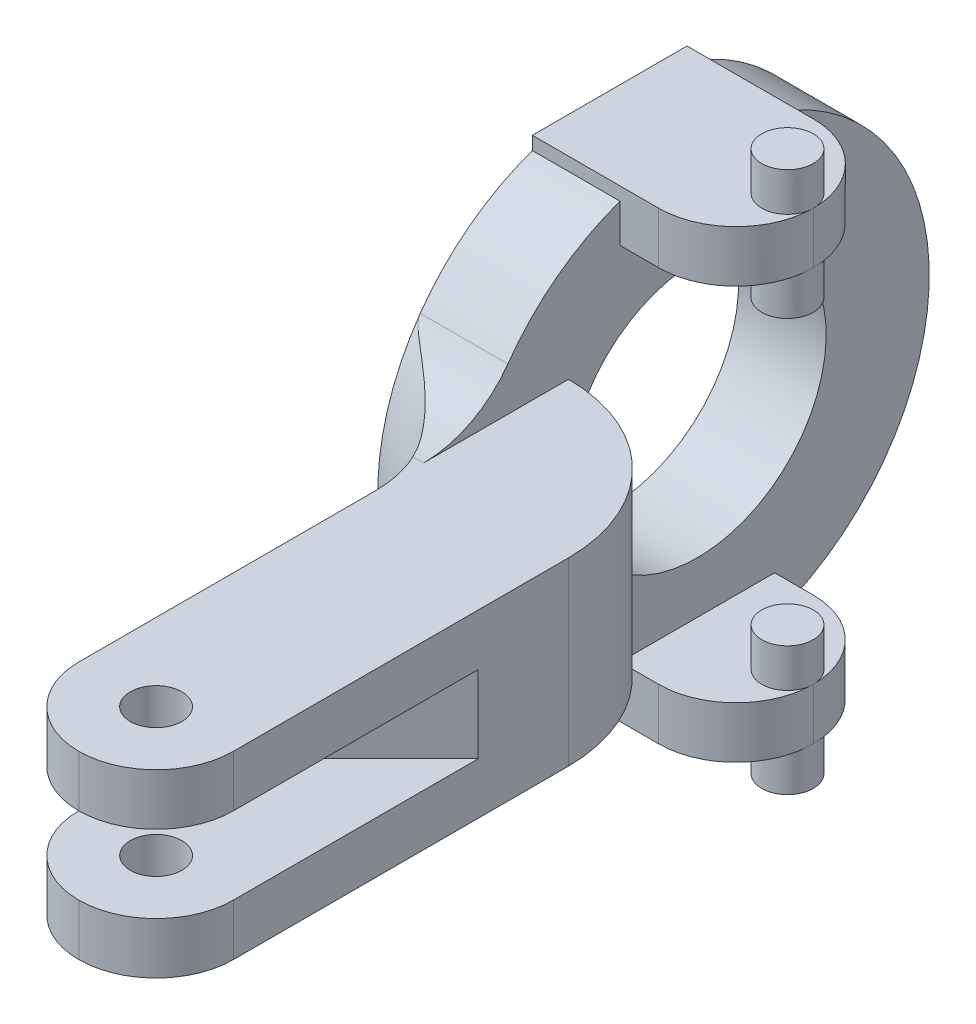
SolidWorks part; units mm, degrees
ref_plane "前视基准面" through (0, 0, 0) normal (0, 0, 1) x (1, 0, 0)
ref_plane "上视基准面" through (0, 0, 0) normal (0, 1, 0) x (1, 0, 0)
ref_plane "右视基准面" through (0, 0, 0) normal (1, 0, 0) x (0, 0, -1)
sketch "Sketch3" plane through (-11.7, 0, 0) normal (1, 0, 0) x (0, 0, -1)
  circle A0 centre (24, -3.8117) radius 4.5
  circle A1 centre (24, -3.8117) radius 2.5
extrude "Extrude1" add sketch "Sketch3" against normal blind 1.7
sketch "Sketch4" plane through (-11.7, 0, 0) normal (1, 0, 0) x (0, 0, -1)
  line L0 (24, -3.8117) -> (-0.088, -3.8117) construction
  line L1 (10.5, -4.8117) -> (21.5, -4.8117)
  line L2 (10.5, -4.8117) -> (10.5, -2.8117)
  line L3 (10.5, -2.8117) -> (21.5, -2.8117)
  line L4 (21.5, -4.8117) -> (21.5, -2.8117)
  line L5 (10.5, -4.8117) -> (21.5, -2.8117) construction
  line L6 (10.5, -2.8117) -> (21.5, -4.8117) construction
  circle A0 centre (24, -3.8117) radius 2.5 construction
  point P0 (16, -3.8117)
  dimension "D1" = 2
  dimension "D2" = 11
extrude "Extrude2" add sketch "Sketch4" along normal blind 2
sketch "Sketch7" plane through (-11.7, 0, 0) normal (-1, 0, 0) x (0, 0, 1)
  line L0 (-10.5, -2.8117) -> (-10.5, -4.8117) construction
  line L1 (-21.5, -5.5617) -> (-10.5, -5.5617)
  line L2 (-21.5, -5.5617) -> (-21.5, -2.0617)
  line L3 (-21.5, -2.0617) -> (-10.5, -2.0617)
  line L4 (-10.5, -5.5617) -> (-10.5, -2.0617)
  line L5 (-21.5, -5.5617) -> (-10.5, -2.0617) construction
  line L6 (-21.5, -2.0617) -> (-10.5, -5.5617) construction
  line L7 (-19.6125, -2.8117) -> (-10.5, -2.8117) construction
  point P0 (-16, -3.8117)
  dimension "D1" = 11
  dimension "D2" = 3.5
  dimension "D3" = 0.75
extrude "Extrude5" add sketch "Sketch7" against normal blind 3
sketch "Sketch8" plane through (0, 0, -10.5) normal (0, 0, 1) x (1, 0, 0)
  line L0 (-11.7, -2.0617) -> (-11.7, -5.5617) construction
  line L1 (-11.7, -4.5617) -> (-8.7, -4.5617)
  line L2 (-11.7, -4.5617) -> (-11.7, -3.0617)
  line L3 (-11.7, -3.0617) -> (-8.7, -3.0617)
  line L4 (-8.7, -4.5617) -> (-8.7, -3.0617)
  line L5 (-11.7, -4.5617) -> (-8.7, -3.0617) construction
  line L6 (-11.7, -3.0617) -> (-8.7, -4.5617) construction
  line L7 (-8.7, -5.5617) -> (-11.7, -5.5617) construction
  point P0 (-10.2, -3.8117)
  dimension "D1" = 3
  dimension "D2" = 1.5
  dimension "D3" = 1
extrude "Cut-Extrude2" cut sketch "Sketch8" against normal blind 3.25
sketch "Sketch9" plane through (0, -2.0617, 0) normal (0, 1, 0) x (1, 0, 0)
  line L0 (-11.7, 10.5) -> (-11.7, 19.8542) construction
  line L1 (-8.7, 10.5) -> (-11.7, 10.5) construction
  circle A0 centre (-10.2, 12) radius 0.5
  point P6 (-10.2, 10.5)
  dimension "D1" = 1.5
  dimension "D2" = 1.5
extrude "Cut-Extrude3" cut sketch "Sketch9" against normal through all
fillet "Fillet1" radius 1.5 4 edges at (-8.7, -5.0617, -10.5) (-11.7, -5.0617, -10.5) (-11.7, -2.5617, -10.5) (-8.7, -2.5617, -10.5)
chamfer "Chamfer1" distance 3 angle 45 2 edges at (-11.7, -3.8117, -13.75) (-8.7, -3.8117, -13.75)
fillet "Fillet4" radius 2 1 edges at (-11.7, -3.8117, -19.5)
fillet "Fillet5" radius 3 1 edges at (-8.7, -3.8117, -21.5)
fillet "Fillet7" radius 2 2 edges at (-12.55, -2.0617, -19.8542) (-12.55, -5.5617, -19.8542)
sketch "Sketch10" plane through (-11.7, 0, 0) normal (1, 0, 0) x (0, 0, -1)
  line L5 (25.5, -0.3117) -> (22.5, -0.3117)
  line L6 (25.5, -8.3117) -> (22.5, -8.3117)
  line L8 (25.5, -8.3117) -> (25.5, -7.3117)
  line L9 (25.5, 0.6883) -> (22.5, 0.6883)
  line L10 (22.5, -8.3117) -> (22.5, -7.3117)
  line L11 (25.5, -8.3117) -> (22.5, 0.6883) construction
  line L12 (25.5, 0.6883) -> (22.5, -8.3117) construction
  line L13 (25.5, -7.3117) -> (22.5, -7.3117)
  line L14 (25.5, -0.3117) -> (25.5, 0.6883)
  line L15 (22.5, -0.3117) -> (22.5, 0.6883)
  point P0 (24, -3.8117)
  dimension "D1" = 3
  dimension "D2" = 9
  dimension "D3" = 1
  dimension "D4" = 1
extrude "Extrude6" add sketch "Sketch10" along normal blind 2.25 and the other way up to surface (1.7 mm away) other way up to face at (-13.4, -1.3117, -24)
sketch "Sketch11" plane through (0, 0.6883, 0) normal (0, 1, 0) x (1, 0, 0)
  line L0 (-9.45, 25.5) -> (-9.45, 22.5) construction
  line L1 (-9.45, 25.5) -> (-13.4, 25.5) construction
  circle A0 centre (-9.95, 24) radius 0.5
  dimension "D1" = 1.5
  dimension "D2" = 1
extrude "Extrude7" add sketch "Sketch11" along normal blind 0.75 and the other way blind 1.75
sketch "Sketch12" plane through (0, -8.3117, 0) normal (0, -1, 0) x (1, 0, 0)
  line L0 (-9.45, -22.5) -> (-13.4, -22.5) construction
  line L1 (-9.45, -22.5) -> (-9.45, -25.5) construction
  circle A0 centre (-9.95, -24) radius 0.5
  dimension "D1" = 1.5
  dimension "D2" = 1
extrude "Extrude8" add sketch "Sketch12" along normal blind 0.75 and the other way blind 1.75
fillet "Fillet11" radius 1.5 4 edges at (-9.45, -7.8117, -25.5) (-9.45, -7.8117, -22.5) (-9.45, 0.1883, -25.5) (-9.45, 0.1883, -22.5)
